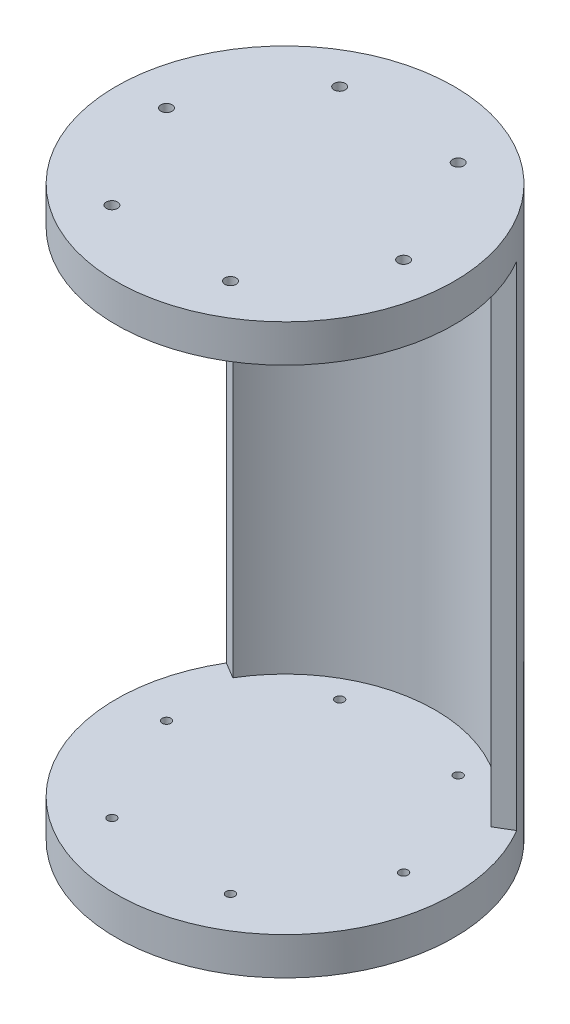
SolidWorks part; units mm, degrees
ref_plane "Front Plane" through (0, 0, 0) normal (0, 0, 1) x (1, 0, 0)
ref_plane "Top Plane" through (0, 0, 0) normal (0, 1, 0) x (1, 0, 0)
ref_plane "Right Plane" through (0, 0, 0) normal (1, 0, 0) x (0, 0, -1)
sketch "Sketch1" plane through (0, 0, 0) normal (0, 1, 0) x (1, 0, 0)
  line L0 (0, 0) -> (-57.995, 34.5373)
  line L1 (0, 0) -> (57.995, 34.5373)
  circle A0 centre (0, 0) radius 60
  circle A1 centre (0, 0) radius 67.5
  dimension "D1" = 135
  dimension "D2" = 120
extrude "Boss-Extrude1" add sketch "Sketch1" along normal blind 197 contours L1 A1 L0 A0 region at (-54.1504, 0, -33.6641)
sketch "Sketch2" plane through (0, 0, 0) normal (0, -1, 0) x (1, 0, 0)
  circle A1 centre (0, 0) radius 67.5
extrude "Boss-Extrude2" add sketch "Sketch2" along normal blind 15
sketch "Sketch3" plane through (0, -15, 0) normal (0, -1, 0) x (1, 0, 0)
  circle A0 centre (22.7274, 44.5361) radius 2.25
  circle A1 centre (49.9331, 2.5855) radius 2.25
  circle A2 centre (27.2057, -41.9506) radius 2.25
  circle A3 centre (-22.7274, -44.5361) radius 2.25
  circle A4 centre (-49.9331, -2.5855) radius 2.25
  circle A5 centre (-27.2057, 41.9506) radius 2.25
  point P16 (0, 0)
  dimension "D1" = 4.5
  dimension "D2" = 50
  dimension "D3" = 6
extrude "Cut-Extrude1" cut sketch "Sketch3" against normal blind 10
sketch "Sketch4" plane through (0, -5, 0) normal (0, -1, 0) x (1, 0, 0)
  circle A0 centre (22.7274, 44.5361) radius 1.75
  circle A1 centre (49.9331, 2.5855) radius 1.75
  circle A2 centre (27.2057, -41.9506) radius 1.75
  circle A3 centre (-22.7274, -44.5361) radius 1.75
  circle A4 centre (-49.9331, -2.5855) radius 1.75
  circle A5 centre (-27.2057, 41.9506) radius 1.75
  point P15 (0, 0)
  dimension "D1" = 3.5
  dimension "D2" = 6
extrude "Cut-Extrude2" cut sketch "Sketch4" against normal blind 14
ref_plane "Plane2" through (0, 98.5, 0) normal (0, 1, 0) x (1, 0, 0)
mirror "Mirror1" about plane through (0, 98.5, 0) normal (0, 1, 0) of "Cut-Extrude1", "Boss-Extrude1", "Boss-Extrude2"
mirror "Mirror2" about plane through (0, 98.5, 0) normal (0, 1, 0) of "Cut-Extrude2"
